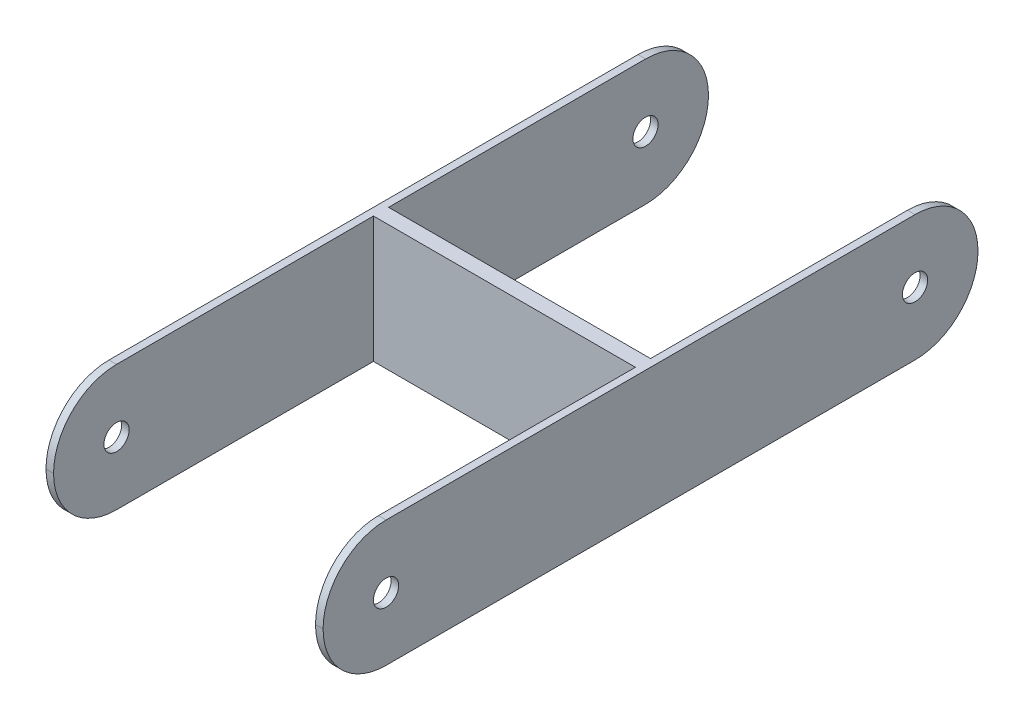
SolidWorks part; units mm, degrees
ref_plane "Front Plane" through (0, 0, 0) normal (0, 0, 1) x (1, 0, 0)
ref_plane "Top Plane" through (0, 0, 0) normal (0, 1, 0) x (1, 0, 0)
ref_plane "Right Plane" through (0, 0, 0) normal (1, 0, 0) x (0, 0, -1)
sketch "Sketch1" plane through (0, 0, 0) normal (0, 1, 0) x (1, 0, 0)
  line L0 (26, -31) -> (26, 32.5)
  line L1 (27.5, -32.5) -> (-27.5, -32.5)
  line L2 (27.5, -32.5) -> (27.5, 32.5)
  line L3 (27.5, 32.5) -> (-27.5, 32.5) construction
  line L4 (-27.5, -32.5) -> (-27.5, 32.5)
  line L5 (27.5, -32.5) -> (-27.5, 32.5) construction
  line L6 (27.5, 32.5) -> (-27.5, -32.5) construction
  line L7 (26, -31) -> (-26, -31)
  line L8 (-26, -31) -> (-26, 32.5)
  line L9 (-27.5, 32.5) -> (-26, 32.5)
  line L10 (26, 32.5) -> (27.5, 32.5)
  point P0 (0, 0)
  dimension "D1" = 65
  dimension "D2" = 55
  dimension "D3" = 1.5
extrude "Boss-Extrude1" add sketch "Sketch1" along normal mid plane 25
fillet "Fillet1" radius 12.5 4 edges at (-26.75, -12.5, -32.5) (-26.75, 12.5, -32.5) (26.75, -12.5, -32.5) (26.75, 12.5, -32.5)
sketch "Sketch2" plane through (0, 0, 0) normal (1, 0, 0) x (0, 0, -1)
  circle A0 centre (20, 0) radius 2.5
extrude "Cut-Extrude1" cut sketch "Sketch2" against normal through all both and the other way through all
mirror "Mirror1" about plane through (27.5, 12.5, 32.5) normal (0, 0, -1) of "Fillet1", "Cut-Extrude1", "Boss-Extrude1"
